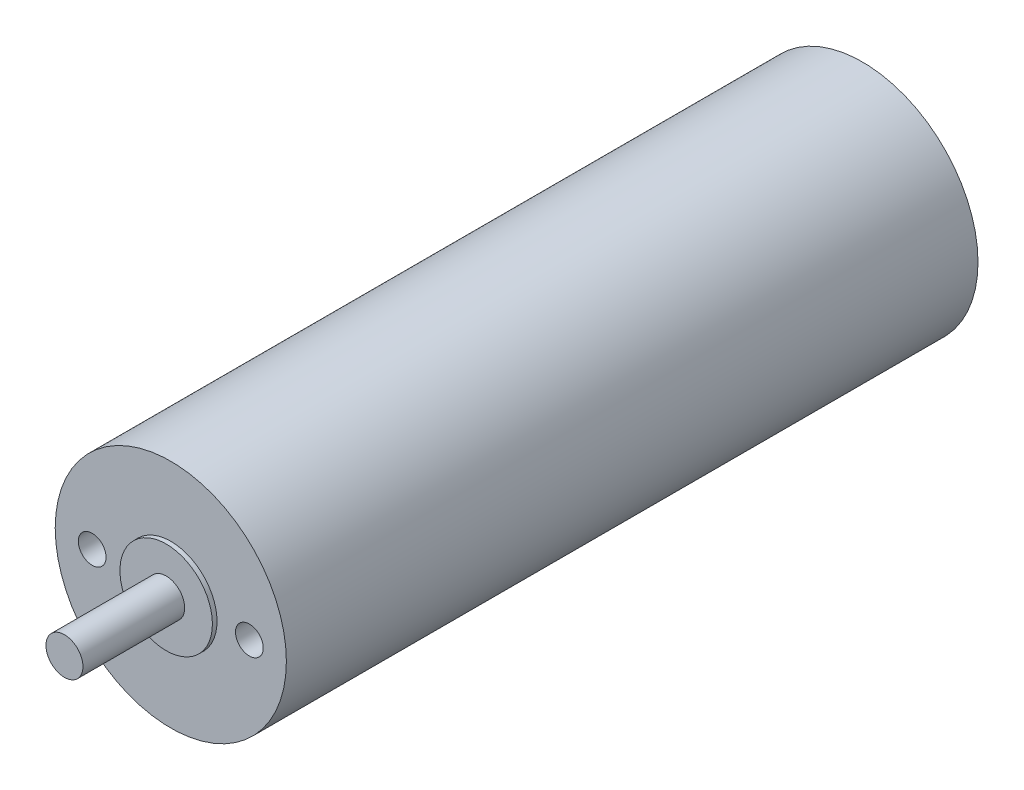
SolidWorks part; units mm, degrees
ref_plane "Front Plane" through (0, 0, 0) normal (0, 0, 1) x (1, 0, 0)
ref_plane "Top Plane" through (0, 0, 0) normal (0, 1, 0) x (1, 0, 0)
ref_plane "Right Plane" through (0, 0, 0) normal (1, 0, 0) x (0, 0, -1)
sketch "Sketch3" plane through (0, 0, 0) normal (0, 0, 1) x (1, 0, 0)
  circle A2 centre (0, 0) radius 12.5
  dimension "D1" = 25
extrude "Boss-Extrude1" add sketch "Sketch3" along normal blind 74.8 contours A2
sketch "Sketch4" plane through (0, 0, 74.8) normal (0, 0, 1) x (1, 0, 0)
  circle A0 centre (0, 0) radius 5
  dimension "D1" = 10
extrude "Boss-Extrude2" add sketch "Sketch4" along normal blind 0.5
sketch "Sketch5" plane through (0, 0, 75.3) normal (0, 0, 1) x (1, 0, 0)
  circle A0 centre (0, 0) radius 2
  dimension "D1" = 4
extrude "Boss-Extrude3" add sketch "Sketch5" along normal blind 11
sketch "Sketch6" plane through (0, 0, 74.8) normal (0, 0, 1) x (1, 0, 0)
  line L0 (-8.5, 0) -> (8.5, 0) construction
  circle A0 centre (-8.5, 0) radius 1.5
  circle A1 centre (8.5, 0) radius 1.5
  point P4 (0, 0)
  dimension "D1" = 17
  dimension "D2" = 3
extrude "Cut-Extrude1" cut sketch "Sketch6" against normal blind 4
ref_axis "Axis1" through (0, 0, 74.8) along (0, 0, -1)
